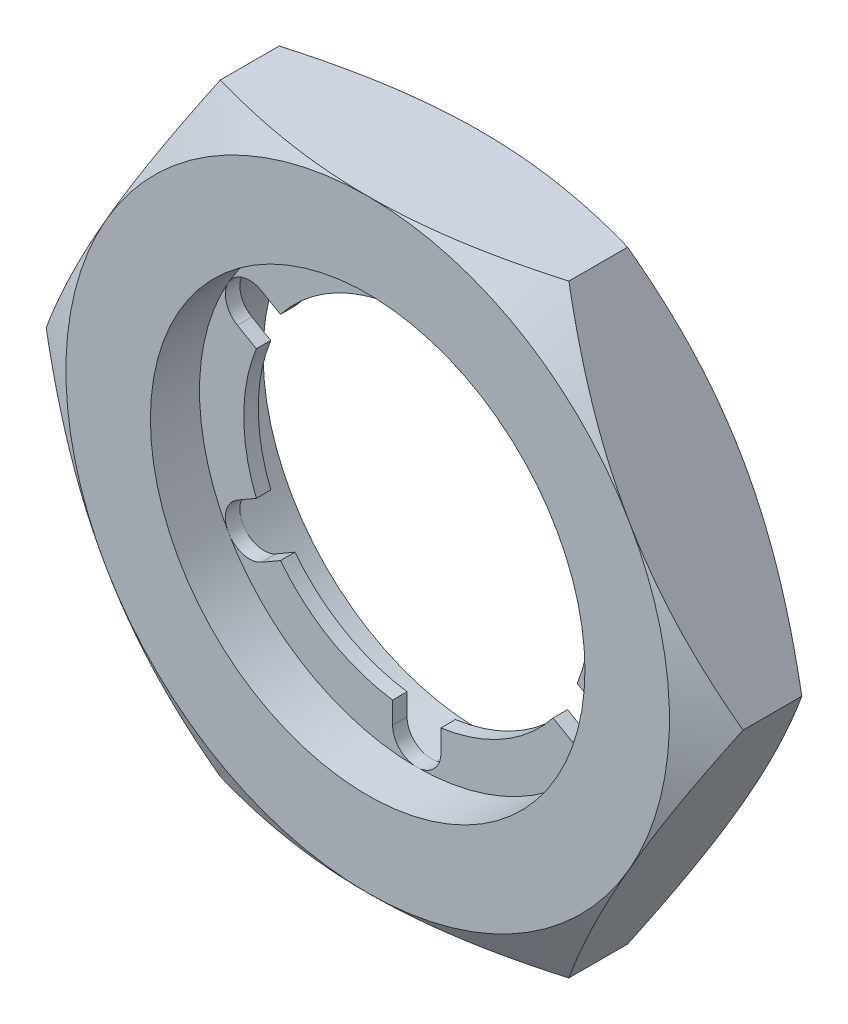
SolidWorks part; units mm, degrees
ref_plane "Front" through (0, 0, 0) normal (0, 0, 1) x (1, 0, 0)
ref_plane "Top" through (0, 0, 0) normal (0, 1, 0) x (1, 0, 0)
ref_plane "Right" through (0, 0, 0) normal (1, 0, 0) x (0, 0, -1)
sketch "Sketch1" plane through (0, 0, 0) normal (0, 0, 1) x (1, 0, 0)
  line L1 (21.6506, -37.5) -> (43.3013, 0)
  line L2 (43.3013, 0) -> (21.6506, 37.5)
  line L3 (21.6506, 37.5) -> (-21.6506, 37.5)
  line L4 (-21.6506, 37.5) -> (-43.3013, 0)
  line L5 (-43.3013, 0) -> (-21.6506, -37.5)
  line L6 (-21.6506, -37.5) -> (21.6506, -37.5)
  circle A0 centre (0, 0) radius 37.5 construction
  circle A1 centre (0, 0) radius 21.5
extrude "BaseNut" add sketch "Sketch1" against normal blind 14
cosmetic thread "ThreadCosmetic1" [suppressed] parameters "D2"=48
sketch "Sketch2" plane through (23.5226, 0, -24.7401) normal (0, 1, 0) x (0, 0, -1)
  line L0 (-11.4787, 23.5226) -> (10.2613, 23.5226) construction
  line L2 (-24.7401, 61.0226) -> (-21.3907, 66.8239)
  line L5 (-21.3907, 66.8239) -> (-24.7401, 66.8239)
  line L6 (-24.7401, 66.8239) -> (-24.7401, 61.0226)
  line L7 (-17.7401, 76.3474) -> (-17.7401, 29.4794) construction
  line L8 (-10.7401, 66.8239) -> (-10.7401, 61.0226)
  line L9 (-14.0894, 66.8239) -> (-10.7401, 66.8239)
  line L10 (-10.7401, 61.0226) -> (-14.0894, 66.8239)
  dimension "D1" = 75
  dimension "D2" = 30
revolve "DoubleChamfer" cut sketch "Sketch2" angle 360 about L0
sketch "Sketch3" plane through (13.7868, 24.2734, 0) normal (0, 0, 1) x (0.866, 0.5, 0)
  line L0 (-43.4799, -14.128) -> (42.6103, -14.128) construction
  line L1 (-0.0765, -11.128) -> (-2.7868, -11.128)
  line L2 (-0.0765, -17.128) -> (-2.7868, -17.128)
  arc A0 (-50.9098, -11.1326) -> (-51.0765, -14.128) centre (-24.0765, -14.128) ccw construction
  arc A1 (-0.0765, -17.128) -> (-0.0765, -11.128) centre (-0.0765, -14.128) ccw
  arc A3 (-2.7868, -17.128) -> (-2.7868, -11.128) centre (-24.0765, -14.128) ccw
  circle A5 centre (-24.0765, -14.128) radius 21.5 construction
  dimension "D1" = 54
extrude "Cut-Extrude1" cut sketch "Sketch3" against normal through all
pattern_circular "CirPattern1" count 6 over 360 about axis through (0, 0, -13.2614) along (0, 0, -1) of "Cut-Extrude1"
ref_plane "Plane1" through (0, 0, -7) normal (0, 0, 1) x (1, 0, 0)
sketch "Sketch4" plane through (12.7705, 22.979, 0) normal (0, 0, 1) x (1, 0, 0)
  circle A1 centre (-12.7705, -22.979) radius 27
  dimension "D1" = 54
extrude "Cut-Extrude2" cut sketch "Sketch4" against normal offset from surface (6.1 mm away) 0.9 up to plane "Plane1"
mirror "Mirror1" about plane through (0, 0, -7) normal (0, 0, 1) of "Cut-Extrude2"
sketch "Sketch5" plane through (0, 0, 0) normal (0, 1, 0) x (1, 0, 0)
  line L0 (21, 8.15) -> (21, 7.65)
  line L1 (21, 7.65) -> (21.5, 7.65)
  line L2 (21.5, 7.65) -> (21.933, 7.9)
  line L3 (21.933, 7.9) -> (21.5, 8.15)
  line L4 (21.5, 8.15) -> (21, 8.15)
  line L5 (0, 20.0501) -> (0, -4.257) construction
  line L6 (23.3827, 7.9) -> (0, 7.9) construction
  dimension "D1" = 0.5
  dimension "D2" = 43
revolve "Cut-Revolve10" [suppressed] cut sketch "Sketch5" angle 360 about L5
pattern_linear "LPattern10" [suppressed] count 3 spacing 0.6 of bodies 107
equation "\"D1@Sketch4\" = \"D1@Sketch3\""
equation "\"D1@Sketch2\" = \"s@Sketch1\""
equation "\"D1@Plane1\"=\"m@BaseNut\"/2"
equation "\"D2@Sketch5\" = \"d@Sketch1\""
equation "\"D1@Sketch5\" = (  \"D2@ThreadCosmetic1\" - \"d@Sketch1\" )  / 10"
equation "\"D3@LPattern10\" = \"D1@Sketch5\" * 1.2"
equation "\"D1@LPattern10\" = \"w@Cut-Extrude2\" / \"D3@LPattern10\" * 2"
